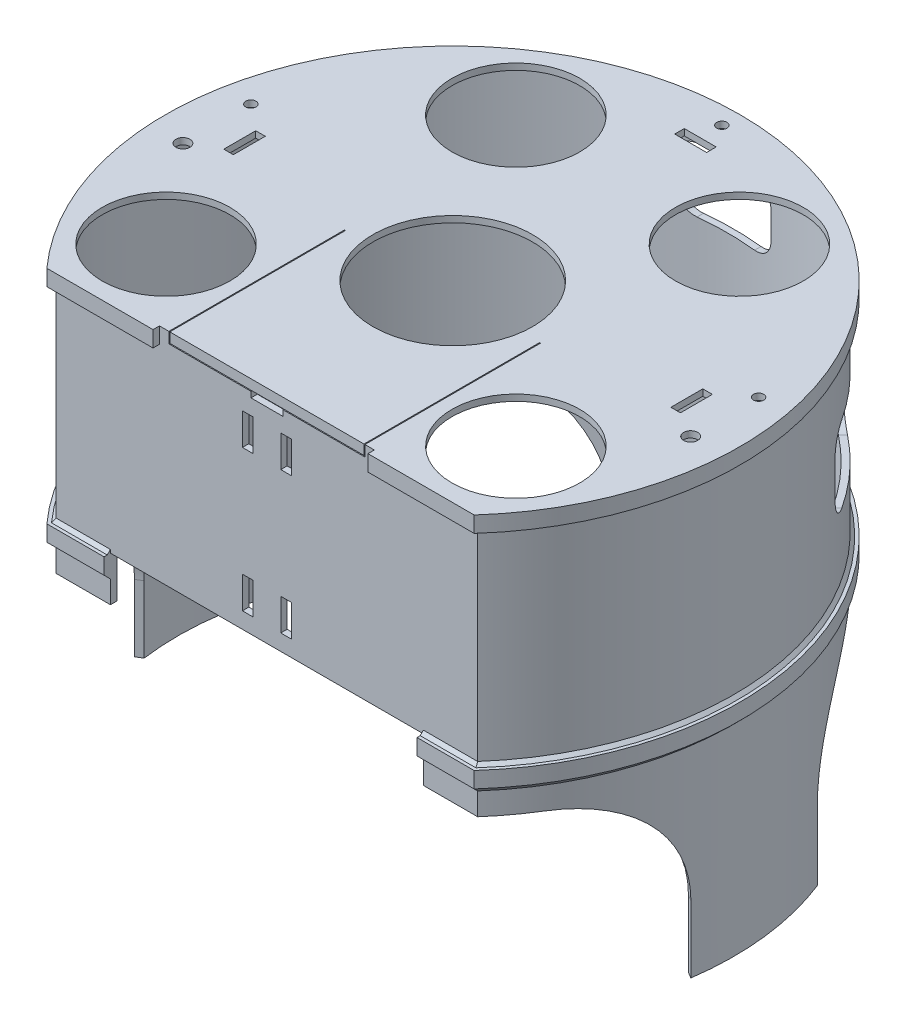
SolidWorks part; units mm, degrees
ref_plane "Front" through (0, 0, 0) normal (0, 0, 1) x (1, 0, 0)
ref_plane "Top" through (0, 0, 0) normal (0, 1, 0) x (1, 0, 0)
ref_plane "Right" through (0, 0, 0) normal (1, 0, 0) x (0, 0, -1)
sketch "Sketch1" plane through (0, 0, 0) normal (0, 1, 0) x (1, 0, 0)
  line L0 (-66.0058, -58.2) -> (66.0058, -58.2)
  line L1 (-65.0965, -56.2) -> (65.0965, -56.2)
  arc A0 (-66.0058, -58.2) -> (66.0058, -58.2) centre (0, 0) cw
  arc A1 (-65.0965, -56.2) -> (65.0965, -56.2) centre (0, 0) cw
  dimension "D1" = 88
  dimension "D3" = 86
  dimension "D2" = 58.2
  dimension "D4" = 56.2
extrude "Extrude1" add sketch "Sketch1" along normal blind 137.3
sketch "Sketch5" plane through (0, 137.3, 0) normal (0, 1, 0) x (1, 0, 0)
  line L0 (-66.0058, -58.2) -> (66.0058, -58.2) construction
  line L1 (-66.0058, -58.2) -> (66.0058, -58.2)
  arc A0 (66.0058, -58.2) -> (-66.0058, -58.2) centre (0, 0) ccw
extrude "Extrude4" add sketch "Sketch5" along normal blind 2
sketch "Sketch6" plane through (0, 0, 58.2) normal (0, 0, 1) x (1, 0, 0)
  line L0 (-66.0058, 0) -> (66.0058, 0) construction
  line L1 (-49, 0) -> (49, 0)
  line L2 (-49, 0) -> (-49, 70)
  line L3 (-49, 70) -> (49, 70)
  line L4 (49, 0) -> (49, 70)
  dimension "D1" = 49
  dimension "D2" = 49
  dimension "D3" = 70
extrude "Extrude5" cut sketch "Sketch6" against normal blind 5
sketch "Sketch8" plane through (0, 139.3, 0) normal (0, 1, 0) x (-1, 0, 0)
  circle A0 centre (79.5, 5) radius 2.2
  circle A1 centre (-79.5, 5) radius 2.2
  dimension "D1" = 4.4
  dimension "D3" = 4.4
  dimension "D5" = 5
  dimension "D2" = 79.5
  dimension "D4" = 79.5
extrude "Extrude7" cut sketch "Sketch8" against normal blind 5
sketch "Sketch9" plane through (0, 0, 58.2) normal (0, 0, 1) x (1, 0, 0)
  line L0 (-66.0058, 139.3) -> (-66.0058, 0) construction
  line L1 (-49, 0) -> (-66.0058, 0)
  line L2 (-49, 0) -> (-49, 56)
  line L3 (-49, 56) -> (-66.0058, 56)
  line L4 (-66.0058, 0) -> (-66.0058, 56)
  dimension "D1" = 56
extrude "Extrude8" cut sketch "Sketch9" against normal blind 5
mirror "Mirror1" about plane through (0, 0, 0) normal (1, 0, 0) of "Extrude8"
sketch "Sketch12" plane through (0, 0, 0) normal (1, 0, 0) x (0, 0, -1)
  line L0 (0, 136) -> (0, 0)
ref_plane "Plane 45" through (0, 0, 0) normal (0.7071, 0, 0.7071) x (0.7071, 0, -0.7071)
ref_plane "Plane 33" through (0, 0, 0) normal (-0.8572, 0, 0.515) x (0.515, 0, 0.8572)
sketch "Sketch13" plane through (0, 0, 0) normal (-0.8572, 0, 0.515) x (0.515, 0, 0.8572)
  line L1 (15.8917, 0) -> (-34.1083, 0)
  line L2 (15.8917, 0) -> (15.8917, 56)
  line L3 (15.8917, 56) -> (-34.1083, 56)
  line L4 (-34.1083, 0) -> (-34.1083, 56)
  dimension "D1" = 56
  dimension "D2" = 50
extrude "Extrude16" cut sketch "Sketch13" along normal blind 100
fillet "Fillet4" radius 35 1 edges at (-86.1696, 56, 11.984)
sketch "Sketch14" plane through (0, 0, 0) normal (0.7071, 0, 0.7071) x (0.7071, 0, -0.7071)
  line L0 (-70.4598, 0) -> (88, 0) construction
  line L1 (-35, 0) -> (35, 0)
  line L2 (-35, 0) -> (-35, 57)
  line L3 (-35, 57) -> (35, 57)
  line L4 (35, 0) -> (35, 57)
  dimension "D1" = 57
  dimension "D2" = 70
  dimension "D3" = 35
extrude "Extrude17" cut sketch "Sketch14" against normal blind 100
fillet "Fillet5" radius 35 2 edges at (-31.5709, 57, -81.0684) (-81.0684, 57, -31.5709)
mirror "Mirror3" about plane through (0, 0, 0) normal (1, 0, 0) of "Fillet5", "Extrude17", "Fillet4", "Extrude16"
ref_plane "Plane6" through (0, 0, 0) normal (-0.7071, 0, 0.7071) x (0.7071, 0, 0.7071)
sketch "Sketch16" plane through (0, 0, 0) normal (-0.7071, 0, 0.7071) x (0.7071, 0, 0.7071)
  line L0 (87.8267, 139.3) -> (-88, 139.3) construction
  line L1 (24, 114.3) -> (-16, 114.3)
  line L2 (24, 114.3) -> (24, 90.3)
  line L3 (24, 90.3) -> (-16, 90.3)
  line L4 (-16, 114.3) -> (-16, 90.3)
  line L5 (-88, 139.3) -> (-88, 57) construction
  dimension "D1" = 40
  dimension "D2" = 24
  dimension "D3" = 25
  dimension "D4" = 72
extrude "Extrude19" cut sketch "Sketch16" against normal blind 100
fillet "Fillet7" radius 6 4 edges at (76.1014, 114.3, -42.1603) (49.1551, 114.3, -71.7826) (76.1014, 90.3, -42.1603) (49.1551, 90.3, -71.7826)
sketch "Sketch17" plane through (0, 0, 0) normal (0, 0, 1) x (1, 0, 0)
  line L0 (0, 0) -> (0, 133.9725) construction
  line L1 (-66.0058, 139.3) -> (66.0058, 139.3) construction
  line L6 (15, 129.3) -> (-15, 129.3)
  line L7 (15, 129.3) -> (15, 109.3)
  line L8 (15, 109.3) -> (-15, 109.3)
  line L9 (-15, 129.3) -> (-15, 109.3)
  dimension "D1" = 15
  dimension "D2" = 15
  dimension "D3" = 10
  dimension "D6" = 20
extrude "Extrude20" cut sketch "Sketch17" against normal blind 100
sketch "Sketch19" plane through (0, 0, 58.2) normal (0, 0, 1) x (1, 0, 0)
  text T0 "IMMORTALS" font "Segoe Print" height in points 36
extrude "Extrude21" [suppressed] cut sketch "Sketch19" against normal up to surface (2 mm away)
sketch "Sketch20" plane through (0, 139.3, 0) normal (0, 1, 0) x (1, 0, 0)
  circle A4 centre (0, 84.2726) radius 1.6
  circle A5 centre (-79.5, 16.2726) radius 1.6
  circle A6 centre (79.5, 16.2726) radius 1.6
  dimension "D1" = 79.5
  dimension "D2" = 16.2726
  dimension "D3" = 84.2726
extrude "Cut-Extrude1" cut sketch "Sketch20" against normal blind 10
sketch "Sketch21" plane through (0, 139.3, 0) normal (0, 1, 0) x (1, 0, 0)
  circle A0 centre (35.0004, 54.772) radius 20
  circle A1 centre (-35.0004, 54.772) radius 20
  circle A2 centre (54.7723, -35) radius 20
  circle A3 centre (-54.7723, -35) radius 20
  circle A4 centre (0, 0) radius 25
extrude "Cut-Extrude2" cut sketch "Sketch21" against normal blind 10 contours A4 | A1 | A0 | A2 | A3
sketch "Sketch23" plane through (0, 139.3, 0) normal (0, 1, 0) x (1, 0, 0)
  line L0 (0, 0) -> (0, -73.988) construction
  line L14 (-30.4, -58.2) -> (-30.4, -3.2)
  line L15 (-66.0058, -58.2) -> (66.0058, -58.2) construction
  line L16 (-30.7, -3.2) -> (-30.7, -58.2)
  line L17 (-30.7, -3.2) -> (-30.4, -3.2)
  line L18 (-30.7, -58.2) -> (-30.4, -58.2)
  line L19 (30.7, -58.2) -> (30.4, -58.2)
  line L20 (30.7, -3.2) -> (30.4, -3.2)
  line L21 (30.7, -3.2) -> (30.7, -58.2)
  line L22 (30.4, -58.2) -> (30.4, -3.2)
  dimension "D1" = 30.4
  dimension "D2" = 0.3
  dimension "D3" = 55
  dimension "D4" = 55
extrude "Cut-Extrude3" cut sketch "Sketch23" against normal blind 2
sketch "Sketch24" plane through (0, 0, 58.2) normal (0, 0, 1) x (1, 0, 0)
  line L0 (0, 136) -> (0, 121.0807) construction
  line L1 (-30.7, 135.9) -> (-5, 135.9)
  line L18 (-30.7, 137.3) -> (-30.7, 135.9)
  line L23 (-5, 135.9) -> (-5, 134.1)
  line L24 (-30.4, 137.3) -> (-30.4, 136.2)
  line L26 (-30.4, 136.2) -> (30.4, 136.2)
  line L27 (-5, 134.1) -> (5, 134.1)
  line L28 (30.4, 137.3) -> (30.4, 136.2)
  line L29 (5, 135.9) -> (5, 134.1)
  line L30 (30.7, 137.3) -> (30.7, 135.9)
  line L31 (30.7, 135.9) -> (5, 135.9)
  line L33 (-30.7, 137.3) -> (-30.4, 137.3)
  line L34 (30.4, 137.3) -> (30.7, 137.3)
  point P12 (0, 134.1)
  point P13 (0, 136.2)
  point P15 (0, 132)
  dimension "D1" = 1.4
  dimension "D2" = 25.7
  dimension "D3" = 1.8
  dimension "D4" = 1.1
extrude "Cut-Extrude4" cut sketch "Sketch24" against normal blind 4
sketch "Sketch25" plane through (0, 139.3, 0) normal (0, 1, 0) x (1, 0, 0)
  line L0 (-66.0058, -58.2) -> (-30.7, -58.2) construction
  line L5 (71.5, -0.2) -> (68.5, 9.8) construction
  line L6 (-71.5, 9.8) -> (-68.5, 9.8)
  line L11 (-71.5, 9.8) -> (-71.5, -0.2)
  line L16 (-71.5, -0.2) -> (-68.5, -0.2)
  line L17 (-68.5, 9.8) -> (-68.5, -0.2)
  line L18 (-71.5, 9.8) -> (-68.5, -0.2) construction
  line L19 (-71.5, -0.2) -> (-68.5, 9.8) construction
  line L20 (71.5, 9.8) -> (68.5, -0.2) construction
  line L21 (68.5, 9.8) -> (68.5, -0.2)
  line L26 (0, 0) -> (0, 76) construction
  line L27 (-5, 77.5) -> (5, 77.5)
  line L28 (-5, 77.5) -> (-5, 74.5)
  line L29 (-5, 74.5) -> (5, 74.5)
  line L30 (5, 77.5) -> (5, 74.5)
  line L31 (-5, 77.5) -> (5, 74.5) construction
  line L32 (-5, 74.5) -> (5, 77.5) construction
  line L33 (71.5, -0.2) -> (68.5, -0.2)
  line L34 (71.5, 9.8) -> (71.5, -0.2)
  line L35 (71.5, 9.8) -> (68.5, 9.8)
  point P0 (-70, 4.8)
  point P12 (70, 4.8)
  dimension "D1" = 70
  dimension "D2" = 63
extrude "Cut-Extrude5" cut sketch "Sketch25" against normal blind 4
fillet "Fillet12" radius 6 4 edges at (-15, 129.3, -85.697) (-15, 109.3, -85.697) (15, 129.3, -85.697) (15, 109.3, -85.697)
sketch "Sketch26" plane through (0, 139.3, 0) normal (0, 1, 0) x (1, 0, 0)
  line L0 (-66.0058, -58.2) -> (-68.6495, -58.2)
  line L1 (66.0058, -58.2) -> (68.6495, -58.2)
  arc A0 (66.0058, -58.2) -> (-66.0058, -58.2) centre (0, 0) ccw
  arc A1 (68.6495, -58.2) -> (-68.6495, -58.2) centre (0, 0) ccw
  dimension "D1" = 180
extrude "Boss-Extrude1" add sketch "Sketch26" against normal blind 5
ref_plane "Plane7" through (0, 70, 0) normal (0, -1, 0) x (-1, 0, 0)
sketch "Sketch27" plane through (0, 70, 0) normal (0, -1, 0) x (-1, 0, 0)
  line L0 (68.6495, -58.2) -> (66.0058, -58.2)
  line L1 (-66.0058, -58.2) -> (-68.6495, -58.2)
  arc A0 (66.0058, -58.2) -> (-66.0058, -58.2) centre (0, 0) ccw
  arc A1 (68.6495, -58.2) -> (-68.6495, -58.2) centre (0, 0) ccw
  dimension "D1" = 176
  dimension "D2" = 180
extrude "Boss-Extrude2" add sketch "Sketch27" along normal blind 5
sketch "Sketch28" plane through (0, 0, 58.2) normal (0, 0, 1) x (1, 0, 0)
  line L0 (-68.6495, 70) -> (-68.6495, 65)
  line L1 (-68.6495, 65) -> (-49, 65)
  line L2 (-49, 70) -> (-49, 56) construction
  line L3 (-88, 65) -> (88, 65) construction
  line L4 (-49, 65) -> (-49, 70)
  line L5 (-1.1, 70) -> (1.1, 70) construction
  line L6 (-49, 70) -> (-68.6495, 70)
  line L12 (-68.6495, 134.3) -> (-33.6495, 134.3)
  line L13 (-88, 134.3) -> (88, 134.3) construction
  line L14 (-33.6495, 134.3) -> (-33.6495, 139.3)
  line L15 (-68.6495, 139.3) -> (-30.7, 139.3) construction
  line L16 (-33.6495, 139.3) -> (-68.6495, 139.3)
  line L17 (-68.6495, 139.3) -> (-68.6495, 134.3)
  line L18 (0, 71.311) -> (0, 117.6032) construction
  line L19 (49, 65) -> (49, 70)
  line L20 (68.6495, 65) -> (49, 65)
  line L21 (68.6495, 70) -> (68.6495, 65)
  line L22 (49, 70) -> (68.6495, 70)
  line L23 (33.6495, 139.3) -> (68.6495, 139.3)
  line L24 (33.6495, 134.3) -> (33.6495, 139.3)
  line L25 (68.6495, 134.3) -> (33.6495, 134.3)
  line L26 (68.6495, 139.3) -> (68.6495, 134.3)
  dimension "D1" = 35
extrude "Boss-Extrude3" add sketch "Sketch28" along normal blind 2
sketch "Sketch29" plane through (0, 139.3, 0) normal (0, 1, 0) x (1, 0, 0)
  circle A0 centre (0, 0) radius 90
  circle A1 centre (0, 0) radius 104.0571
extrude "Cut-Extrude6" cut sketch "Sketch29" against normal blind 200
sketch "Sketch30" plane through (0, 0, 58.2) normal (0, 0, 1) x (1, 0, 0)
  line L0 (-33.6495, 139.3) -> (-66.9026, 139.3) construction
  line L1 (-7.6644, 129.2759) -> (-4.3471, 129.2759)
  line L2 (-7.6644, 129.2759) -> (-7.6644, 119.3241)
  line L3 (-7.6644, 119.3241) -> (-4.3471, 119.3241)
  line L4 (-4.3471, 129.2759) -> (-4.3471, 119.3241)
  line L5 (-7.6644, 129.2759) -> (-4.3471, 119.3241) construction
  line L6 (-7.6644, 119.3241) -> (-4.3471, 129.2759) construction
  line L7 (-66.0058, 134.3) -> (-66.0058, 70) construction
  line L8 (-66.0058, 102.15) -> (40.4275, 102.15) construction
  line L9 (-7.6644, 84.9759) -> (-4.3471, 84.9759)
  line L10 (-4.3471, 75.0241) -> (-4.3471, 84.9759)
  line L11 (-7.6644, 75.0241) -> (-4.3471, 75.0241)
  line L12 (-7.6644, 75.0241) -> (-7.6644, 84.9759)
  line L13 (0, 134.1) -> (0, 77.4104) construction
  line L14 (-5, 134.1) -> (5, 134.1) construction
  line L15 (7.6644, 75.0241) -> (7.6644, 84.9759)
  line L16 (7.6644, 75.0241) -> (4.3471, 75.0241)
  line L17 (4.3471, 75.0241) -> (4.3471, 84.9759)
  line L18 (7.6644, 84.9759) -> (4.3471, 84.9759)
  line L19 (7.6644, 119.3241) -> (4.3471, 119.3241)
  line L20 (4.3471, 129.2759) -> (4.3471, 119.3241)
  line L21 (7.6644, 129.2759) -> (4.3471, 129.2759)
  line L22 (7.6644, 129.2759) -> (7.6644, 119.3241)
  point P0 (-6.0058, 124.3)
  dimension "D1" = 15
  dimension "D2" = 60
extrude "Cut-Extrude7" cut sketch "Sketch30" against normal blind 10
chamfer "Chamfer2" distance 2 angle 45 3 edges at (0, 65, -88) (57.5029, 65, 58.2) (-57.5029, 65, 58.2)
chamfer "Chamfer4" distance 1 angle 45 3 edges at (57.5029, 70, 58.2) (0, 70, -88) (-57.5029, 70, 58.2)
